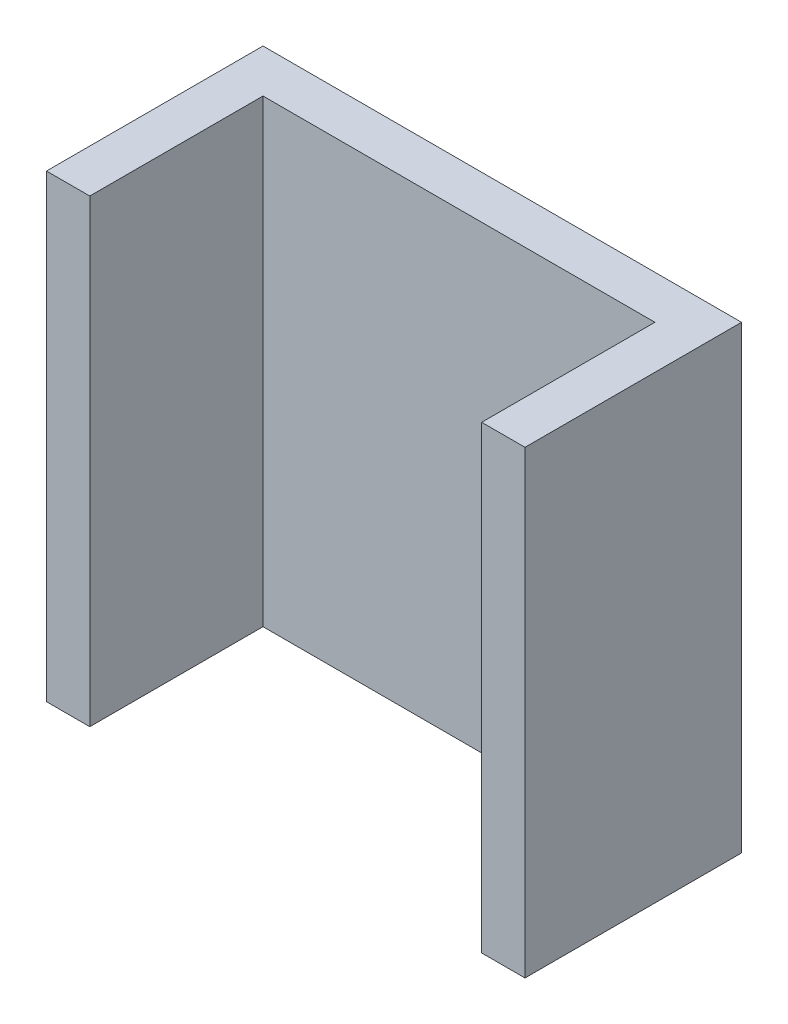
SolidWorks part; units mm, degrees
ref_plane "Front Plane" through (0, 0, 0) normal (0, 0, 1) x (1, 0, 0)
ref_plane "Top Plane" through (0, 0, 0) normal (0, 1, 0) x (1, 0, 0)
ref_plane "Right Plane" through (0, 0, 0) normal (1, 0, 0) x (0, 0, -1)
sketch "Sketch1" plane through (0, 0, 0) normal (1, 0, 0) x (0, 0, -1)
  line L0 (-145, 145) -> (-145, 255)
  line L2 (-145, 0) -> (-145, 145)
  line L3 (-145, 145) -> (0, 145) construction
  line L4 (0, 0) -> (0, 145)
  line L5 (-145, 255) -> (0, 255)
  line L6 (0, 255) -> (0, 145)
  line L7 (0, -145) -> (420.2376, 355.8197) construction
  line L8 (0, -145) -> (-93.2042, -33.9236) construction
  line L9 (94.1529, -32.793) -> (175.1688, -32.793) construction
  line L10 (-93.2042, -33.9236) -> (741.3522, 221.2259) construction
  line L11 (301.5271, 86.7579) -> (438.6224, 86.7579) construction
  line L12 (0, -145) -> (-176.7331, -199.0327) construction
  line L13 (-93.2042, -33.9236) -> (-193.8224, -153.8356) construction
  line L14 (274.6455, 249.3185) -> (274.6455, -80.6815)
  line L15 (274.6455, -80.6815) -> (168.3686, 167.5225)
  arc A0 (0, -145) -> (-145, 0) centre (0, 0) cw
  parabola Q0 (0, 0) -> (300.3031, 267.8046) focus (0, -145) apex (-49.0614, -159.9996)
  parabola Q1 (0, -145) -> (593.7614, 75.583) focus (-93.2042, -33.9236) apex (-147.8987, -99.1059)
  dimension "D1" = 145
  dimension "D2" = 110
  dimension "D3" = 50
  dimension "D4" = 17
  dimension "D5" = 80
  dimension "D6" = 330
  dimension "D7" = 270
sketch "Sketch2" plane through (0, 0, 0) normal (1, 0, 0) x (0, 0, -1)
  line L0 (-145, 145) -> (0, 145) construction
  line L1 (0, 255) -> (0, 145) construction
  line L2 (-145, 255) -> (0, 255) construction
  line L3 (-145, 145) -> (-145, 255) construction
  line L4 (274.6455, -80.6815) -> (168.3686, 167.5225) construction
  line L5 (274.6455, 249.3185) -> (274.6455, -80.6815) construction
  line L6 (0, 0) -> (0, 145) construction
  line L7 (-145, 0) -> (-145, 145) construction
  line L8 (-145, 145) -> (0, 145) construction
  line L9 (0, 255) -> (0, 145)
  line L10 (-145, 255) -> (0, 255)
  line L11 (-145, 145) -> (-145, 255)
  line L12 (274.6455, -80.6815) -> (168.3686, 167.5225)
  line L13 (274.6455, 249.3185) -> (274.6455, -80.6815) construction
  line L14 (0, 0) -> (0, 145)
  line L15 (-145, 0) -> (-145, 145)
  line L16 (-145.6, 0) -> (-145.6, 145)
  line L20 (0.6, 1.8139) -> (0.6, 145)
  line L21 (274.2922, 249.8034) -> (274.6455, 249.3185)
  line L22 (274.6455, -80.6815) -> (274.8642, -81.2403)
  line L23 (168.3686, 167.5225) -> (172.0457, 169.097)
  line L24 (168.3686, 167.5225) -> (274.6455, -80.6815)
  line L25 (172.0457, 169.097) -> (278.3226, -79.1071)
  line L26 (274.6455, -80.6815) -> (278.3226, -79.1071)
  line L27 (0, 145) -> (0.6, 145)
  line L28 (-145, 145) -> (-145.6, 145)
  line L29 (-155, 145) -> (-155, 265)
  line L30 (0.6, 255.6) -> (0.6, 145) construction
  line L31 (-145.6, 255.6) -> (0.6, 255.6) construction
  line L32 (-145.6, 145) -> (-145.6, 255.6) construction
  line L33 (-155, 265) -> (10, 265)
  line L34 (10, 265) -> (10, 145)
  line L35 (-155, 145) -> (-145, 145)
  line L36 (10, 145) -> (0, 145)
  line L38 (0, 145) -> (-145, 145)
  line L39 (0, 145) -> (0, 144.7)
  line L40 (0, 144.7) -> (-145, 144.7)
  line L41 (-145, 145) -> (-145, 144.7)
  arc A0 (-145, 0) -> (0, -145) centre (0, 0) ccw construction
  arc A1 (-145, 0) -> (0, -145) centre (0, 0) ccw
  arc A2 (-145.6, 0) -> (0, -145.6) centre (0, 0) ccw
  parabola Q0 (0, -145) -> (593.7614, 75.583) focus (-93.2042, -33.9236) apex (-147.8987, -99.1059) construction
  parabola Q1 (0, 0) -> (300.3031, 267.8046) focus (0, -145) apex (-49.0614, -159.9996) construction
  parabola Q2 (0, -145) -> (274.6455, -80.6815) focus (-93.2042, -33.9236) apex (-147.8987, -99.1059)
  parabola Q3 (0, 0) -> (274.6455, 249.3185) focus (0, -145) apex (-49.0614, -159.9996)
  spline S0 degree 1 poles (0, -145.6) (274.8642, -81.2403) knots 0 0 1 1 construction
  spline S1 degree 1 poles (0.6, 1.8139) (274.2922, 249.8034) knots 0 0 1 1 construction
  spline S2 degree 3 poles (274.8642, -81.2403) (273.1576, -81.9083) (269.7338, -83.2415) (262.9417, -85.8581) (254.5103, -89.0531) (244.501, -92.7603) (231.2945, -97.5361) (215.05, -103.1917) (195.9774, -109.4761) (177.3259, -115.2579) (153.0186, -122.2971) (123.6866, -129.8396) (90.1715, -136.8804) (63.6442, -141.072) (43.2642, -143.4196) (28.3972, -144.6775) (16.3662, -145.3064) (6.9341, -145.5581) (2.32, -145.6) (0, -145.6) knots 0.50387 0.50387 0.50387 0.50387 0.503942 0.504013 0.504156 0.5043 0.504443 0.504729 0.505015 0.505302 0.505588 0.506161 0.506734 0.507306 0.507593 0.507879 0.508165 0.508308 0.508452 0.508452 0.508452 0.508452
  spline S3 degree 3 poles (0.6, 1.8139) (1.4319, 2.9295) (3.0981, 5.1446) (6.5223, 9.6202) (10.937, 15.2496) (16.4614, 22.0765) (24.1255, 31.2688) (34.2669, 42.9303) (47.3338, 57.1972) (61.2981, 71.7376) (81.1138, 91.4895) (108.1271, 116.8637) (138.1321, 143.1509) (163.9312, 164.7288) (184.1782, 181.1862) (205.3228, 197.9178) (223.6912, 212.0892) (238.8352, 223.5637) (250.4165, 232.2373) (260.2579, 239.5249) (268.2359, 245.3839) (272.2758, 248.3346) (274.2922, 249.8034) knots 0.504877 0.504877 0.504877 0.504877 0.504963 0.505049 0.50522 0.505391 0.505563 0.505905 0.506248 0.50659 0.506933 0.507618 0.508303 0.508646 0.508989 0.509331 0.509674 0.509845 0.510016 0.510188 0.510273 0.510359 0.510359 0.510359 0.510359
  dimension "D2" = 4
  dimension "D4" = 0.3
  dimension "D1" = 0.6
  dimension "D3" = 10
sketch "Sketch3" plane through (0, 0, 0) normal (1, 0, 0) x (0, 0, -1)
  line L0 (274.6455, -80.6815) -> (168.3686, 167.5225) construction
  line L1 (168.3686, 167.5225) -> (172.0457, 169.097) construction
  line L2 (172.0457, 169.097) -> (278.3226, -79.1071) construction
  line L3 (274.6455, -80.6815) -> (278.3226, -79.1071) construction
  line L4 (168.3686, 167.5225) -> (274.6455, -80.6815) construction
  line L5 (0, 255) -> (0, 145) construction
  line L6 (-145, 255) -> (0, 255) construction
  line L7 (-145, 145) -> (-145, 255) construction
  line L8 (-145, 0) -> (-145, 145) construction
  line L9 (-145, 145) -> (-145.6, 145) construction
  line L10 (-145.6, 0) -> (-145.6, 145) construction
  line L11 (274.6455, -80.6815) -> (274.8642, -81.2403) construction
  line L12 (-155, 145) -> (-145, 145) construction
  line L13 (-155, 145) -> (-155, 265) construction
  line L14 (-155, 265) -> (10, 265) construction
  line L15 (10, 265) -> (10, 145) construction
  line L16 (10, 145) -> (0, 145) construction
  line L17 (0, 145) -> (-145, 145) construction
  line L18 (0, 145) -> (0, 144.7) construction
  line L19 (0, 144.7) -> (-145, 144.7) construction
  line L20 (-145, 145) -> (-145, 144.7) construction
  line L21 (0, 0) -> (0, 145) construction
  line L22 (274.2922, 249.8034) -> (274.6455, 249.3185) construction
  line L23 (0.6, 1.8139) -> (0.6, 145) construction
  line L24 (0, 145) -> (0.6, 145) construction
  line L25 (274.6455, -80.6815) -> (168.3686, 167.5225)
  line L26 (168.3686, 167.5225) -> (172.0457, 169.097)
  line L27 (172.0457, 169.097) -> (278.3226, -79.1071)
  line L28 (274.6455, -80.6815) -> (278.3226, -79.1071)
  line L29 (168.3686, 167.5225) -> (274.6455, -80.6815)
  line L30 (0, 255) -> (0, 145)
  line L31 (-145, 255) -> (0, 255)
  line L32 (-145, 145) -> (-145, 255)
  line L33 (-145, 0) -> (-145, 145)
  line L34 (-145, 145) -> (-145.6, 145)
  line L35 (-145.6, 0) -> (-145.6, 145)
  line L36 (274.6455, -80.6815) -> (274.8642, -81.2403)
  line L37 (-155, 145) -> (-145, 145)
  line L38 (-155, 145) -> (-155, 265)
  line L39 (-155, 265) -> (10, 265)
  line L40 (10, 265) -> (10, 145)
  line L41 (10, 145) -> (0, 145)
  line L42 (0, 145) -> (-145, 145)
  line L43 (0, 145) -> (0, 144.7)
  line L44 (0, 144.7) -> (-145, 144.7)
  line L45 (-145, 145) -> (-145, 144.7)
  line L46 (0, 0) -> (0, 145)
  line L47 (274.2922, 249.8034) -> (274.6455, 249.3185)
  line L48 (0.6, 1.8139) -> (0.6, 145)
  line L49 (0, 145) -> (0.6, 145)
  line L50 (-155, 575) -> (-155, 695)
  line L51 (-145, 575) -> (-145, 685)
  line L52 (-155, 695) -> (10, 695)
  line L53 (-145, 685) -> (0, 685)
  line L54 (10, 695) -> (10, 575)
  line L55 (0, 685) -> (0, 575)
  line L56 (10, 575) -> (0, 575)
  line L57 (0.6, 431.8139) -> (0.6, 575)
  line L58 (0, 430) -> (0, 575)
  line L59 (0, 574.7) -> (-145, 574.7)
  line L60 (-145, 430) -> (-145, 575)
  line L61 (-145.6, 430) -> (-145.6, 575)
  line L62 (-155, 575) -> (-145, 575)
  line L63 (274.6455, 349.3185) -> (274.8642, 348.7597)
  line L64 (274.6455, 349.3185) -> (278.3226, 350.8929)
  line L65 (274.6455, 349.3185) -> (168.3686, 597.5225)
  line L66 (172.0457, 599.097) -> (278.3226, 350.8929)
  line L67 (168.3686, 597.5225) -> (172.0457, 599.097)
  line L68 (274.2922, 679.8034) -> (274.6455, 679.3185)
  line L69 (0, 575) -> (-145, 575)
  line L70 (-155, 1005) -> (-155, 1125)
  line L71 (-145, 1005) -> (-145, 1115)
  line L72 (-155, 1125) -> (10, 1125)
  line L73 (-145, 1115) -> (0, 1115)
  line L74 (10, 1125) -> (10, 1005)
  line L75 (0, 1115) -> (0, 1005)
  line L76 (10, 1005) -> (0, 1005)
  line L77 (0.6, 861.8139) -> (0.6, 1005)
  line L78 (0, 860) -> (0, 1005)
  line L79 (0, 1004.7) -> (-145, 1004.7)
  line L80 (-145, 860) -> (-145, 1005)
  line L81 (-145.6, 860) -> (-145.6, 1005)
  line L82 (-155, 1005) -> (-145, 1005)
  line L83 (274.6455, 779.3185) -> (274.8642, 778.7597)
  line L84 (274.6455, 779.3185) -> (278.3226, 780.8929)
  line L85 (274.6455, 779.3185) -> (168.3686, 1027.5225)
  line L86 (172.0457, 1029.097) -> (278.3226, 780.8929)
  line L87 (168.3686, 1027.5225) -> (172.0457, 1029.097)
  line L88 (274.2922, 1109.8034) -> (274.6455, 1109.3185)
  line L89 (0, 1005) -> (-145, 1005)
  arc A0 (-145, 0) -> (0, -145) centre (0, 0) ccw construction
  arc A1 (-145.6, 0) -> (0, -145.6) centre (0, 0) ccw construction
  arc A2 (-145, 0) -> (0, -145) centre (0, 0) ccw
  arc A3 (-145.6, 0) -> (0, -145.6) centre (0, 0) ccw
  arc A4 (-145, 430) -> (0, 285) centre (0, 430) ccw
  arc A5 (-145.6, 430) -> (0, 284.4) centre (0, 430) ccw
  arc A6 (-145, 860) -> (0, 715) centre (0, 860) ccw
  arc A7 (-145.6, 860) -> (0, 714.4) centre (0, 860) ccw
  parabola Q0 (0, -145) -> (274.6455, -80.6815) focus (-93.2042, -33.9236) apex (-147.8987, -99.1059) construction
  parabola Q1 (0, 0) -> (274.6455, 249.3185) focus (0, -145) apex (-49.0614, -159.9996) construction
  parabola Q2 (0, -145) -> (274.6455, -80.6815) focus (-93.2042, -33.9236) apex (-147.8987, -99.1059)
  parabola Q3 (0, 0) -> (274.6455, 249.3185) focus (0, -145) apex (-49.0614, -159.9996)
  parabola Q4 (0, 430) -> (274.6455, 679.3185) focus (0, 285) apex (-49.0614, 270.0004)
  parabola Q5 (0, 285) -> (274.6455, 349.3185) focus (-93.2042, 396.0764) apex (-147.8987, 330.8941)
  parabola Q6 (0, 860) -> (274.6455, 1109.3185) focus (0, 715) apex (-49.0614, 700.0004)
  parabola Q7 (0, 715) -> (274.6455, 779.3185) focus (-93.2042, 826.0764) apex (-147.8987, 760.8941)
  spline S0 degree 3 poles (-2532.6565, -1138.1182) (517.166, 27.2131) (377.0621, -41.8945) (262.9417, -85.8581) (254.5103, -89.0531) (244.501, -92.7603) (231.2945, -97.5361) (215.05, -103.1917) (195.9774, -109.4761) (177.3259, -115.2579) (153.0186, -122.2971) (123.6866, -129.8396) (90.1715, -136.8804) (63.6442, -141.072) (43.2642, -143.4196) (28.3972, -144.6775) (16.3662, -145.3064) (-89.7923, -148.1384) (-144.0863, -112.0401) (-2997.9045, -39.5411) knots 0.499345 0.499345 0.499345 0.499345 0.503942 0.504013 0.504156 0.5043 0.504443 0.504729 0.505015 0.505302 0.505588 0.506161 0.506734 0.507306 0.507593 0.507879 0.508165 0.508308 0.514325 0.514325 0.514325 0.514325 only from (274.8642, -81.2403) to (0, -145.6) construction
  spline S1 degree 3 poles (-1751.4871, -2433.1925) (-55.1342, -100.2952) (-43.2482, -55.4331) (6.5223, 9.6202) (10.937, 15.2496) (16.4614, 22.0765) (24.1255, 31.2688) (34.2669, 42.9303) (47.3338, 57.1972) (61.2981, 71.7376) (81.1138, 91.4895) (108.1271, 116.8637) (138.1321, 143.1509) (163.9312, 164.7288) (184.1782, 181.1862) (205.3228, 197.9178) (223.6912, 212.0892) (238.8352, 223.5637) (250.4165, 232.2373) (260.2579, 239.5249) (377.9568, 325.9622) (533.0374, 426.7515) (-2133.1319, -1539.7711) knots 0.50024 0.50024 0.50024 0.50024 0.504963 0.505049 0.50522 0.505391 0.505563 0.505905 0.506248 0.50659 0.506933 0.507618 0.508303 0.508646 0.508989 0.509331 0.509674 0.509845 0.510016 0.510188 0.510273 0.515071 0.515071 0.515071 0.515071 only from (0.6, 1.8139) to (274.2922, 249.8034) construction
  spline S2 degree 3 poles (274.8642, -81.2403) (273.1576, -81.9083) (269.7338, -83.2415) (262.9417, -85.8581) (254.5103, -89.0531) (244.501, -92.7603) (231.2945, -97.5361) (215.05, -103.1917) (195.9774, -109.4761) (177.3259, -115.2579) (153.0186, -122.2971) (123.6866, -129.8396) (90.1715, -136.8804) (63.6442, -141.072) (43.2642, -143.4196) (28.3972, -144.6775) (16.3662, -145.3064) (6.9341, -145.5581) (2.32, -145.6) (0, -145.6) knots 0.50387 0.50387 0.50387 0.50387 0.503942 0.504013 0.504156 0.5043 0.504443 0.504729 0.505015 0.505302 0.505588 0.506161 0.506734 0.507306 0.507593 0.507879 0.508165 0.508308 0.508452 0.508452 0.508452 0.508452
  spline S3 degree 3 poles (0.6, 1.8139) (1.4319, 2.9295) (3.0981, 5.1446) (6.5223, 9.6202) (10.937, 15.2496) (16.4614, 22.0765) (24.1255, 31.2688) (34.2669, 42.9303) (47.3338, 57.1972) (61.2981, 71.7376) (81.1138, 91.4895) (108.1271, 116.8637) (138.1321, 143.1509) (163.9312, 164.7288) (184.1782, 181.1862) (205.3228, 197.9178) (223.6912, 212.0892) (238.8352, 223.5637) (250.4165, 232.2373) (260.2579, 239.5249) (268.2359, 245.3839) (272.2758, 248.3346) (274.2922, 249.8034) knots 0.504877 0.504877 0.504877 0.504877 0.504963 0.505049 0.50522 0.505391 0.505563 0.505905 0.506248 0.50659 0.506933 0.507618 0.508303 0.508646 0.508989 0.509331 0.509674 0.509845 0.510016 0.510188 0.510273 0.510359 0.510359 0.510359 0.510359
  spline S4 degree 3 poles (0.6, 431.8139) (1.4319, 432.9295) (3.0981, 435.1446) (6.5223, 439.6202) (10.937, 445.2496) (16.4614, 452.0765) (24.1255, 461.2688) (34.2669, 472.9303) (47.3338, 487.1972) (61.2981, 501.7376) (81.1138, 521.4895) (108.1271, 546.8637) (138.1321, 573.1509) (163.9312, 594.7288) (184.1782, 611.1862) (205.3228, 627.9178) (223.6912, 642.0892) (238.8352, 653.5637) (250.4165, 662.2373) (260.2579, 669.5249) (268.2359, 675.3839) (272.2758, 678.3346) (274.2922, 679.8034) knots 0.504877 0.504877 0.504877 0.504877 0.504963 0.505049 0.50522 0.505391 0.505563 0.505905 0.506248 0.50659 0.506933 0.507618 0.508303 0.508646 0.508989 0.509331 0.509674 0.509845 0.510016 0.510188 0.510273 0.510359 0.510359 0.510359 0.510359
  spline S5 degree 3 poles (274.8642, 348.7597) (273.1576, 348.0917) (269.7338, 346.7585) (262.9417, 344.1419) (254.5103, 340.9469) (244.501, 337.2397) (231.2945, 332.4639) (215.05, 326.8083) (195.9774, 320.5239) (177.3259, 314.7421) (153.0186, 307.7029) (123.6866, 300.1604) (90.1715, 293.1196) (63.6442, 288.928) (43.2642, 286.5804) (28.3972, 285.3225) (16.3662, 284.6936) (6.9341, 284.4419) (2.32, 284.4) (0, 284.4) knots 0.50387 0.50387 0.50387 0.50387 0.503942 0.504013 0.504156 0.5043 0.504443 0.504729 0.505015 0.505302 0.505588 0.506161 0.506734 0.507306 0.507593 0.507879 0.508165 0.508308 0.508452 0.508452 0.508452 0.508452
  spline S6 degree 3 poles (0.6, 861.8139) (1.4319, 862.9295) (3.0981, 865.1446) (6.5223, 869.6202) (10.937, 875.2496) (16.4614, 882.0765) (24.1255, 891.2688) (34.2669, 902.9303) (47.3338, 917.1972) (61.2981, 931.7376) (81.1138, 951.4895) (108.1271, 976.8637) (138.1321, 1003.1509) (163.9312, 1024.7288) (184.1782, 1041.1862) (205.3228, 1057.9178) (223.6912, 1072.0892) (238.8352, 1083.5637) (250.4165, 1092.2373) (260.2579, 1099.5249) (268.2359, 1105.3839) (272.2758, 1108.3346) (274.2922, 1109.8034) knots 0.504877 0.504877 0.504877 0.504877 0.504963 0.505049 0.50522 0.505391 0.505563 0.505905 0.506248 0.50659 0.506933 0.507618 0.508303 0.508646 0.508989 0.509331 0.509674 0.509845 0.510016 0.510188 0.510273 0.510359 0.510359 0.510359 0.510359
  spline S7 degree 3 poles (274.8642, 778.7597) (273.1576, 778.0917) (269.7338, 776.7585) (262.9417, 774.1419) (254.5103, 770.9469) (244.501, 767.2397) (231.2945, 762.4639) (215.05, 756.8083) (195.9774, 750.5239) (177.3259, 744.7421) (153.0186, 737.7029) (123.6866, 730.1604) (90.1715, 723.1196) (63.6442, 718.928) (43.2642, 716.5804) (28.3972, 715.3225) (16.3662, 714.6936) (6.9341, 714.4419) (2.32, 714.4) (0, 714.4) knots 0.50387 0.50387 0.50387 0.50387 0.503942 0.504013 0.504156 0.5043 0.504443 0.504729 0.505015 0.505302 0.505588 0.506161 0.506734 0.507306 0.507593 0.507879 0.508165 0.508308 0.508452 0.508452 0.508452 0.508452
  dimension "D1" = 3
extrude "Boss-Extrude1" add sketch "Sketch3" against normal blind 1250 contours S3 L48 L41 L43 L46 Q3 L47 | L41 L40 L39 L38 L37 L34 L32 L31 L30 | L44 L43 L42 L33 | S2 L36 Q2 A2 L33 L34 L35 A3 | L25 L28 L27 L26 | S5 L63 Q5 A4 L60 L62 L61 A5 | L67 L65 L64 L66 | S4 L57 L56 L58 Q4 L68 | L50 L62 L51 L53 L55 L56 L54 L52 | L58 L69 L60 L59 | L87 L85 L84 L86 | S7 L83 Q7 A6 L80 L82 L81 A7 | S6 L77 L76 L78 Q6 L88 | L78 L89 L80 L79 | L70 L82 L71 L73 L75 L76 L74 L72
sketch "Sketch4" plane through (0, 0, 0) normal (1, 0, 0) x (0, 0, -1)
  line L0 (-155, 1125) -> (10, 1125) construction
  line L1 (-180, 1150) -> (278.3226, 1150)
  line L2 (-180, 1150) -> (-180, -170.6)
  line L3 (-180, -170.6) -> (278.3226, -170.6)
  line L4 (278.3226, 1150) -> (278.3226, 1109.3185)
  line L5 (-155, 1005) -> (-155, 1125) construction
  line L6 (274.6455, 1109.3185) -> (278.3226, 1109.3185)
  line L7 (274.6455, 679.3185) -> (278.3226, 679.3185)
  line L8 (274.6455, 249.3185) -> (278.3226, 249.3185)
  line L9 (278.3226, 679.3185) -> (278.3226, 780.8929)
  line L10 (278.3226, -170.6) -> (278.3226, -79.1071)
  line L11 (278.3226, 249.3185) -> (278.3226, 350.8929)
  line L12 (274.6455, 1108.3185) -> (279.3226, 1108.3185)
  line L13 (279.3226, 1151) -> (279.3226, 1108.3185)
  line L14 (-181, 1151) -> (279.3226, 1151)
  line L15 (-181, 1151) -> (-181, -171.6)
  line L16 (-181, -171.6) -> (279.3226, -171.6)
  line L17 (279.3226, -171.6) -> (279.3226, -79.1071)
  line L18 (274.6455, 248.3185) -> (279.3226, 248.3185)
  line L19 (279.3226, 248.3185) -> (279.3226, 350.8929)
  line L20 (274.6455, 678.3185) -> (279.3226, 678.3185)
  line L21 (279.3226, 678.3185) -> (279.3226, 780.8929)
  line L22 (274.6455, 1108.3185) -> (274.6455, 1109.3185)
  line L23 (278.3226, 780.8929) -> (279.3226, 780.8929)
  line L24 (274.6455, 678.3185) -> (274.6455, 679.3185)
  line L25 (279.3226, 350.8929) -> (278.3226, 350.8929)
  line L26 (274.6455, 248.3185) -> (274.6455, 249.3185)
  line L27 (279.3226, -79.1071) -> (278.3226, -79.1071)
  dimension "D1" = 25
  dimension "D2" = 25
  dimension "D3" = 25
  dimension "D4" = 1
extrude "Boss-Extrude2" add sketch "Sketch4" against normal blind 1250 separate body
sketch "Sketch5" plane through (0, 0, 0) normal (1, 0, 0) x (0, 0, -1)
  line L1 (-181, 1151) -> (279.3226, 1151)
  line L2 (-181, 1151) -> (-181, -171.6)
  line L3 (-181, -171.6) -> (279.3226, -171.6)
  line L4 (279.3226, 1151) -> (279.3226, -171.6)
extrude "Boss-Extrude3" add sketch "Sketch5" along normal blind 10 separate body
sketch "Sketch6" plane through (-1250, 0, 0) normal (-1, 0, 0) x (0, 0, 1)
  line L4 (181, 1151) -> (-279.3226, 1151)
  line L5 (-279.3226, 1151) -> (-279.3226, -171.6)
  line L6 (-279.3226, -171.6) -> (181, -171.6)
  line L7 (181, -171.6) -> (181, 1151)
  line L8 (181, 1151) -> (-279.3226, 1151)
  line L9 (-279.3226, 1151) -> (-279.3226, -171.6)
  line L10 (-279.3226, -171.6) -> (181, -171.6)
  line L11 (181, -171.6) -> (181, 1151)
  dimension "D1" = 0
extrude "Boss-Extrude5" add sketch "Sketch6" along normal blind 10 separate body
sketch "Sketch7" plane through (10, 0, 0) normal (1, 0, 0) x (0, 0, -1)
  line L0 (-145, 145) -> (-145, 255) construction
  line L2 (-145, 255) -> (0, 255) construction
  circle A0 centre (-72.5, 200) radius 50
  circle A1 centre (-72.5, -53.7009) radius 50
  circle A2 centre (-72.5, 630) radius 50
  circle A3 centre (-72.5, 376.2991) radius 50
  circle A4 centre (-72.5, 1060) radius 50
  circle A5 centre (-72.5, 806.2991) radius 50
  dimension "D1" = 100
  dimension "D2" = 100
  dimension "D3" = 72.5
  dimension "D4" = 55
  dimension "D5" = 3
sketch "Sketch8" plane through (-1260, 0, 0) normal (-1, 0, 0) x (0, 0, 1)
  circle A1 centre (72.5, 1060) radius 50
  circle A2 centre (72.5, 1060) radius 50
  circle A3 centre (72.5, 376.2991) radius 50
  circle A4 centre (72.5, 376.2991) radius 50
  circle A5 centre (72.5, 630) radius 50
  circle A6 centre (72.5, 630) radius 50
  circle A7 centre (72.5, -53.7009) radius 50
  circle A8 centre (72.5, -53.7009) radius 50
  circle A9 centre (72.5, 200) radius 50
  circle A10 centre (72.5, 200) radius 50
  circle A11 centre (72.5, 806.2991) radius 50
  circle A12 centre (72.5, 806.2991) radius 50
  dimension "D1" = 0
  dimension "D2" = 0
  dimension "D3" = 0
  dimension "D4" = 0
  dimension "D5" = 0
  dimension "D6" = 0
ref_plane "Plane1" through (0, 0, 72.5) normal (0, 0, 1) x (1, 0, 0)
sketch "Sketch10" plane through (-1260, 0, 0) normal (-1, 0, 0) x (0, 0, 1)
  circle A1 centre (72.5, 200) radius 50 construction
  circle A3 centre (72.5, 200) radius 50
sketch "Sketch12" plane through (10, 0, 0) normal (1, 0, 0) x (0, 0, -1)
  circle A0 centre (-72.5, 630) radius 50 construction
  circle A1 centre (-72.5, 630) radius 50
sketch "Sketch14" plane through (10, 0, 0) normal (1, 0, 0) x (0, 0, -1)
  circle A0 centre (-72.5, -53.7009) radius 50 construction
  circle A1 centre (-72.5, -53.7009) radius 50
  circle A2 centre (-72.5, -53.7009) radius 51
  dimension "D1" = 102
ref_plane "Plane2" through (0, 1060, 0) normal (0, 1, 0) x (1, 0, 0)
sketch "Sketch17" plane through (-1260, 0, 0) normal (-1, 0, 0) x (0, 0, 1)
  circle A0 centre (72.5, 1060) radius 50 construction
  circle A1 centre (72.5, 1060) radius 50
  circle A2 centre (72.5, 1060) radius 51
ref_plane "Plane3" through (0, -53.7009, 0) normal (0, 1, 0) x (1, 0, 0)
sketch "Sketch13" plane through (0, 0, 181) normal (0, 0, 1) x (1, 0, 0)
  line L0 (-1250, 1151) -> (0, 1151) construction
  line L1 (-1535, 1651) -> (275, 1651)
  line L2 (-1535, 1651) -> (-1535, -471.6)
  line L3 (-1535, -471.6) -> (275, -471.6)
  line L4 (275, 1651) -> (275, -471.6)
  line L5 (-1250, -171.6) -> (0, -171.6) construction
  line L6 (-1260, -171.6) -> (-1260, 1151) construction
  line L7 (0, 1151) -> (0, -171.6) construction
  dimension "D1" = 500
  dimension "D2" = 300
  dimension "D3" = 275
  dimension "D4" = 275
extrude "Boss-Extrude6" add sketch "Sketch13" along normal blind 200
sketch "Sketch20" plane through (0, 1651, 0) normal (0, 1, 0) x (1, 0, 0)
  line L1 (-1535, -181) -> (-1735, -181)
  line L2 (-1535, -181) -> (-1535, -1181)
  line L3 (-1535, -1181) -> (-1735, -1181)
  line L4 (-1735, -181) -> (-1735, -1181)
  line L5 (275, -181) -> (475, -181)
  line L6 (275, -181) -> (275, -1181)
  line L7 (275, -1181) -> (475, -1181)
  line L8 (475, -181) -> (475, -1181)
  dimension "D1" = 200
  dimension "D2" = 1000
extrude "Boss-Extrude7" add sketch "Sketch20" against normal through all
sketch "Sketch22" plane through (10, 0, 0) normal (1, 0, 0) x (0, 0, -1)
  circle A4 centre (-72.5, 376.2991) radius 50 construction
  circle A5 centre (-72.5, 376.2991) radius 50
sketch "Sketch23" plane through (10, 0, 0) normal (1, 0, 0) x (0, 0, -1)
  circle A2 centre (-72.5, 1060) radius 50 construction
  circle A3 centre (-72.5, 1060) radius 50
sketch "Sketch25" plane through (-1260, 0, 0) normal (-1, 0, 0) x (0, 0, 1)
  circle A0 centre (72.5, 200) radius 50 construction
  circle A1 centre (72.5, 200) radius 50
  circle A3 centre (72.5, 200) radius 51
sketch "Sketch26" plane through (-1260, 0, 0) normal (-1, 0, 0) x (0, 0, 1)
  circle A2 centre (72.5, 806.2991) radius 50 construction
  circle A3 centre (72.5, 806.2991) radius 50
sketch "Sketch31" plane through (0, 1060, 0) normal (0, 1, 0) x (1, 0, 0)
  line L0 (10, -72.5) -> (215, -72.5)
  line L1 (10, -122.5) -> (10, -22.5) construction
  line L2 (-55, -72.5) -> (55, -72.5) construction
  line L3 (215, -72.5) -> (215, -472.5)
  line L4 (275, -381) -> (275, -1181) construction
  dimension "D1" = 400
  dimension "D2" = 60
sketch "Sketch32" plane through (0, 0, 72.5) normal (0, 0, 1) x (1, 0, 0)
  line L0 (-1260, 200) -> (-1460, 200)
  line L1 (-1460, 200) -> (-1460, 806.2991)
  line L2 (-1260, 806.2991) -> (-1460, 806.2991)
  dimension "D1" = 200
sweep "Sweep13" add profiles "Sketch25" path "Sketch32"
sketch "Sketch34" plane through (0, -53.7009, 0) normal (0, 1, 0) x (1, 0, 0)
  line L0 (215, -72.5) -> (215, -472.5) construction
  line L1 (10, -72.5) -> (215, -72.5) construction
  line L2 (215, -72.5) -> (215, -472.5)
  line L3 (10, -72.5) -> (215, -72.5)
sweep "Sweep14" add profiles "Sketch14" path "Sketch34"
sweep "Sweep-Thin13" add profiles "Sketch23" path "Sketch31" parameters "D1"=1
sketch "Sketch35" plane through (-1260, 0, 0) normal (-1, 0, 0) x (0, 0, 1)
  line L4 (181, -171.6) -> (181, 1151)
  line L5 (181, 1151) -> (-279.3226, 1151)
  line L6 (-279.3226, 1151) -> (-279.3226, -171.6)
  line L7 (-279.3226, -171.6) -> (181, -171.6)
  line L8 (181, -171.6) -> (181, 1151)
  line L9 (181, 1151) -> (-279.3226, 1151)
  line L10 (-279.3226, 1151) -> (-279.3226, -171.6)
  line L11 (-279.3226, -171.6) -> (181, -171.6)
  circle A2 centre (72.5, 630) radius 50 construction
  circle A3 centre (72.5, 630) radius 50
  dimension "D1" = 0
extrude "Extrude-Thin3" add sketch "Sketch35" along normal up to surface (200 mm away) separate body thin
sketch "Sketch36" plane through (0, 0, 72.5) normal (0, 0, 1) x (1, 0, 0)
  line L0 (10, 376.2991) -> (110, 376.2991)
  line L1 (110, 376.2991) -> (110, -53.7009)
  dimension "D1" = 100
sweep "Sweep-Thin14" add profiles "Sketch22" path "Sketch36" parameters "D1"=1
